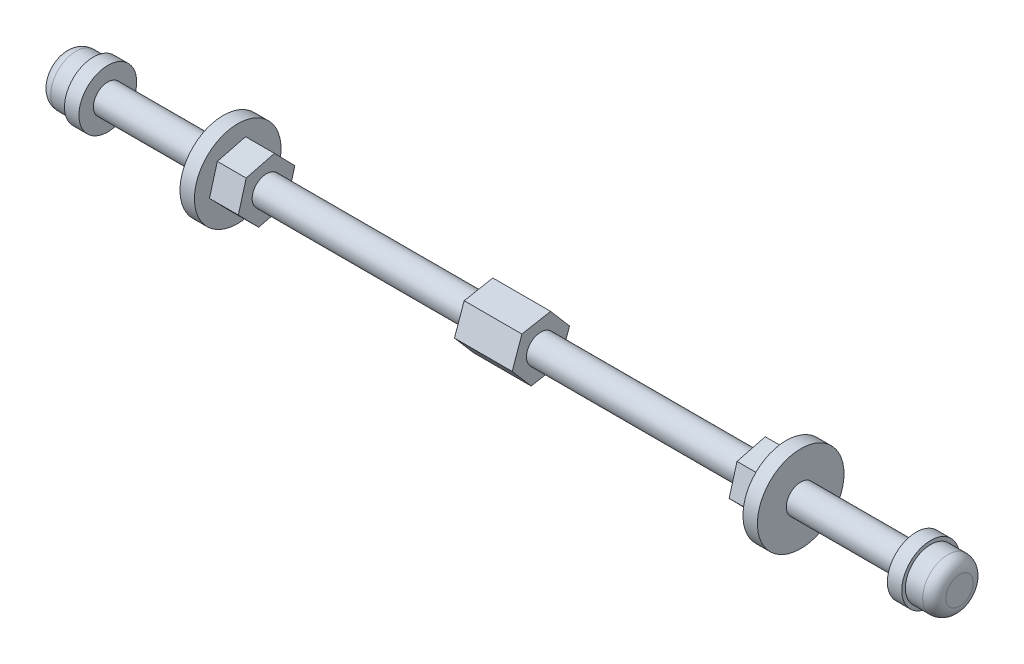
SolidWorks part; units mm, degrees
ref_plane "Front Plane" through (0, 0, 0) normal (0, 0, 1) x (1, 0, 0)
ref_plane "Top Plane" through (0, 0, 0) normal (0, 1, 0) x (1, 0, 0)
ref_plane "Right Plane" through (0, 0, 0) normal (1, 0, 0) x (0, 0, -1)
sketch "Sketch2" plane through (0, 0, 0) normal (1, 0, 0) x (0, 0, -1)
  line L1 (4.1712, -4.8748) -> (6.3073, 1.175)
  line L2 (6.3073, 1.175) -> (2.1361, 6.0498)
  line L3 (2.1361, 6.0498) -> (-4.1712, 4.8748)
  line L4 (-4.1712, 4.8748) -> (-6.3073, -1.175)
  line L5 (-6.3073, -1.175) -> (-2.1361, -6.0498)
  line L6 (-2.1361, -6.0498) -> (4.1712, -4.8748)
  circle A1 centre (0, 0) radius 5.5563 construction
  dimension "D2" = 5.5562
extrude "Boss-Extrude1" add sketch "Sketch2" along normal blind 6.35 and the other way blind 6.35
sketch "Sketch3" plane through (6.35, 0, 0) normal (1, 0, 0) x (0, 0, -1)
  circle A0 centre (0, 0) radius 3.175
  dimension "D1" = 6.35
extrude "Boss-Extrude2" add sketch "Sketch3" along normal blind 47.625 and the other way blind 66.675
sketch "Sketch4" plane through (53.975, 0, 0) normal (1, 0, 0) x (0, 0, -1)
  line L1 (4.4881, -4.5847) -> (6.2145, 1.5945)
  line L2 (6.2145, 1.5945) -> (1.7264, 6.1792)
  line L3 (1.7264, 6.1792) -> (-4.4881, 4.5847)
  line L4 (-4.4881, 4.5847) -> (-6.2145, -1.5945)
  line L5 (-6.2145, -1.5945) -> (-1.7264, -6.1792)
  line L6 (-1.7264, -6.1792) -> (4.4881, -4.5847)
  circle A0 centre (0, 0) radius 5.5563 construction
  dimension "D1" = 5.5562
extrude "Boss-Extrude3" add sketch "Sketch4" along normal blind 6.35
sketch "Sketch5" plane through (60.325, 0, 0) normal (1, 0, 0) x (0, 0, -1)
  circle A0 centre (0, 0) radius 9.525
  dimension "D1" = 19.05
extrude "Boss-Extrude4" add sketch "Sketch5" along normal blind 3.175
mirror "Mirror1" about plane through (0, 0, 0) normal (1, 0, 0) of "Boss-Extrude3", "Boss-Extrude4"
sketch "Sketch7" plane through (63.5, 0, 0) normal (1, 0, 0) x (0, 0, -1)
  circle A0 centre (0, 0) radius 3.175
  dimension "D1" = 6.35
extrude "Boss-Extrude5" add sketch "Sketch7" along normal blind 25.4
sketch "Sketch8" plane through (88.9, 0, 0) normal (1, 0, 0) x (0, 0, -1)
  circle A0 centre (0, 0) radius 6.35
  dimension "D1" = 12.7
extrude "Boss-Extrude6" add sketch "Sketch8" along normal blind 3.175
sketch "Sketch9" plane through (92.075, 0, 0) normal (1, 0, 0) x (0, 0, -1)
  circle A0 centre (0, 0) radius 5.5562
  dimension "D1" = 11.1125
extrude "Boss-Extrude7" add sketch "Sketch9" along normal blind 6.35
fillet "Fillet1" radius 2.54 1 edges at (98.425, 0, -5.5562)
mirror "Mirror2" about plane through (0, 0, 0) normal (1, 0, 0) of "Fillet1", "Boss-Extrude7", "Boss-Extrude6", "Boss-Extrude5"
